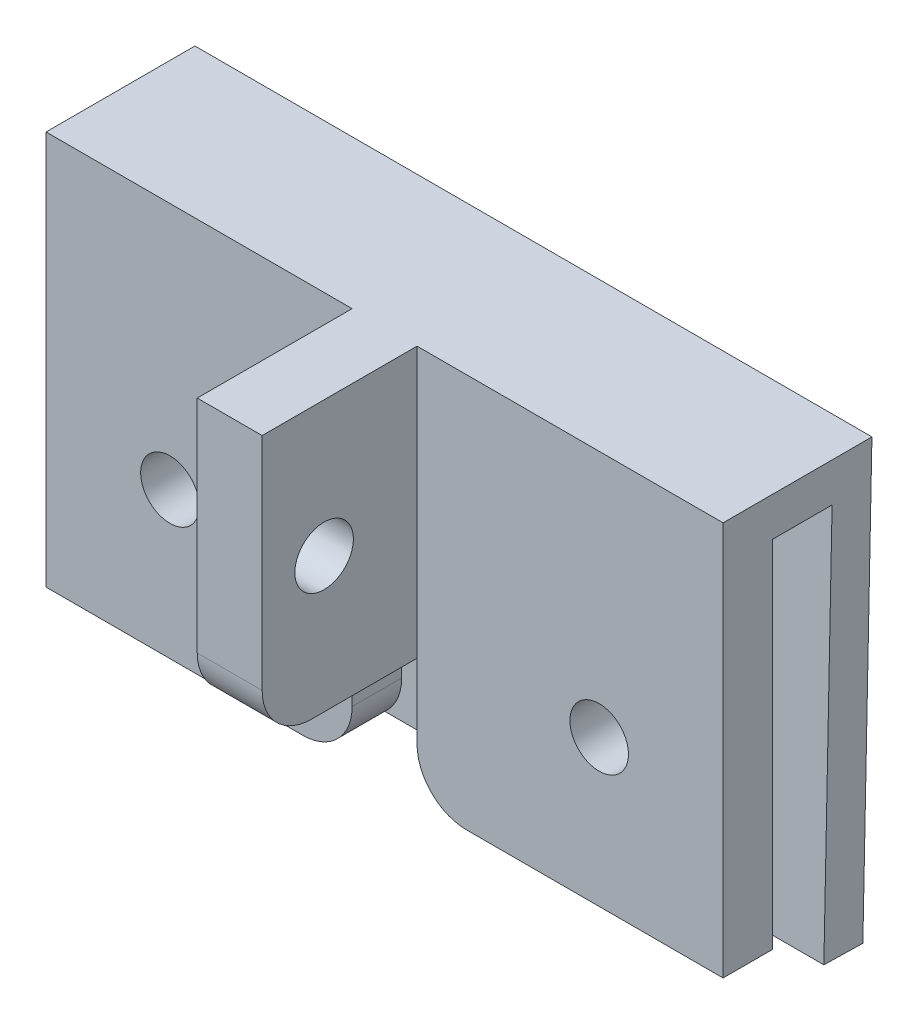
SolidWorks part; units mm, degrees
ref_plane "Front Plane" through (0, 0, 0) normal (0, 0, 1) x (1, 0, 0)
ref_plane "Top Plane" through (0, 0, 0) normal (0, 1, 0) x (1, 0, 0)
ref_plane "Right Plane" through (0, 0, 0) normal (1, 0, 0) x (0, 0, -1)
sketch "Sketch1" plane through (0, 0, 0) normal (0, 0, 1) x (1, 0, 0)
  line L0 (0, 10.102) -> (0, -10.102) construction
  line L1 (-17.35, 10.102) -> (17.35, 10.102)
  line L2 (-17.35, 10.102) -> (-17.35, -10.102)
  line L3 (-17.35, -10.102) -> (17.35, -10.102)
  line L4 (17.35, 10.102) -> (17.35, -10.102)
  line L5 (-17.35, -3.752) -> (17.35, -3.752) construction
  line L6 (-1.6637, -10.102) -> (-1.6637, -3.752)
  line L7 (-1.6637, -3.752) -> (1.6637, -3.752)
  line L8 (1.6637, -3.752) -> (1.6637, -10.102)
  line L9 (-11, -2.598) -> (11, -2.598) construction
  circle A0 centre (-11, -2.598) radius 1.5
  circle A1 centre (11, -2.598) radius 1.5
  point P14 (0, -3.752)
  point P19 (0, -2.598)
  point P23 (0, 0)
  dimension "D3" = 3
  dimension "D1" = 22
  dimension "D2" = 1.154
  dimension "D4" = 12.7
  dimension "D5" = 6.35
  dimension "D6" = 3.3274
  dimension "D7" = 6.35
extrude "Boss-Extrude1" add sketch "Sketch1" along normal blind 2.54 contours L7 L8 L3 L4 L1 L2 L6 A1 A0 region at (0, 0.275, 0)
sketch "Sketch2" plane through (0, 0, 2.54) normal (0, 0, 1) x (1, 0, 0)
  line L0 (-17.35, 10.102) -> (17.35, 10.102) construction
  line L1 (-1.6637, -3.752) -> (1.6637, -3.752)
  line L2 (-1.6637, -3.752) -> (-1.6637, 10.102)
  line L3 (-1.6637, 10.102) -> (1.6637, 10.102)
  line L4 (1.6637, -3.752) -> (1.6637, 10.102)
extrude "Boss-Extrude2" add sketch "Sketch2" along normal blind 7.9375
sketch "Sketch3" plane through (-1.6637, 0, 0) normal (-1, 0, 0) x (0, 0, 1)
  line L0 (10.4775, 10.102) -> (10.4775, -3.752) construction
  line L2 (2.54, 10.102) -> (2.54, -10.102) construction
  circle A1 centre (7.3025, 3.175) radius 1.5
  point P5 (10.4775, 3.175)
  dimension "D1" = 3
  dimension "D2" = 4.7625
extrude "Cut-Extrude1" cut sketch "Sketch3" against normal through all
fillet "Fillet1" radius 2.54 1 edges at (0, -3.752, 10.4775)
fillet "Fillet3" radius 2.54 2 edges at (1.6637, -10.102, 1.27) (-1.6637, -10.102, 1.27)
sketch "Sketch4" plane through (17.35, 0, 0) normal (1, 0, 0) x (0, 0, -1)
  line L0 (0, 10.102) -> (5.0903, 10.102)
  line L1 (5.0903, 10.102) -> (4.6666, -10.1438)
  line L2 (4.6666, -10.1438) -> (2.667, -10.102)
  line L3 (2.667, -10.102) -> (3.048, 8.102)
  line L4 (3.048, 8.102) -> (0, 8.102)
  line L5 (0, 10.102) -> (0, -10.102) construction
  line L6 (4.6666, -10.1438) -> (4.6247, -12.1434)
  line L7 (4.6247, -12.1434) -> (2.6252, -12.1016)
  line L8 (2.6252, -12.1016) -> (2.667, -10.102)
  line M9 (0, -10.102) -> (0, 10.102)
  dimension "D1" = 2
  dimension "D2" = 2
  dimension "D3" = 3.048
  dimension "D4" = 2.667
  dimension "D5" = 2
extrude "Boss-Extrude3" add sketch "Sketch4" against normal up to surface (34.7 mm away) contours L8 L7 L6 L2 | L4 L3 L2 L1 L0 M9 region at (17.35, 1.1902, -3.57) region at (17.35, -11.1227, -3.6459) up to face at (-17.35, 0, 1.27)
equation "\"bottomThickness\"= .220in"
equation "\"wallThickness\"= .125in"
equation "\"D6@Sketch1\"=\"wallThickness\"+.006in"
equation "\"D3@Sketch4\"=\"wallThickness\"-.005in"
equation "\"D4@Sketch4\"=\"wallThickness\"-.02in"
